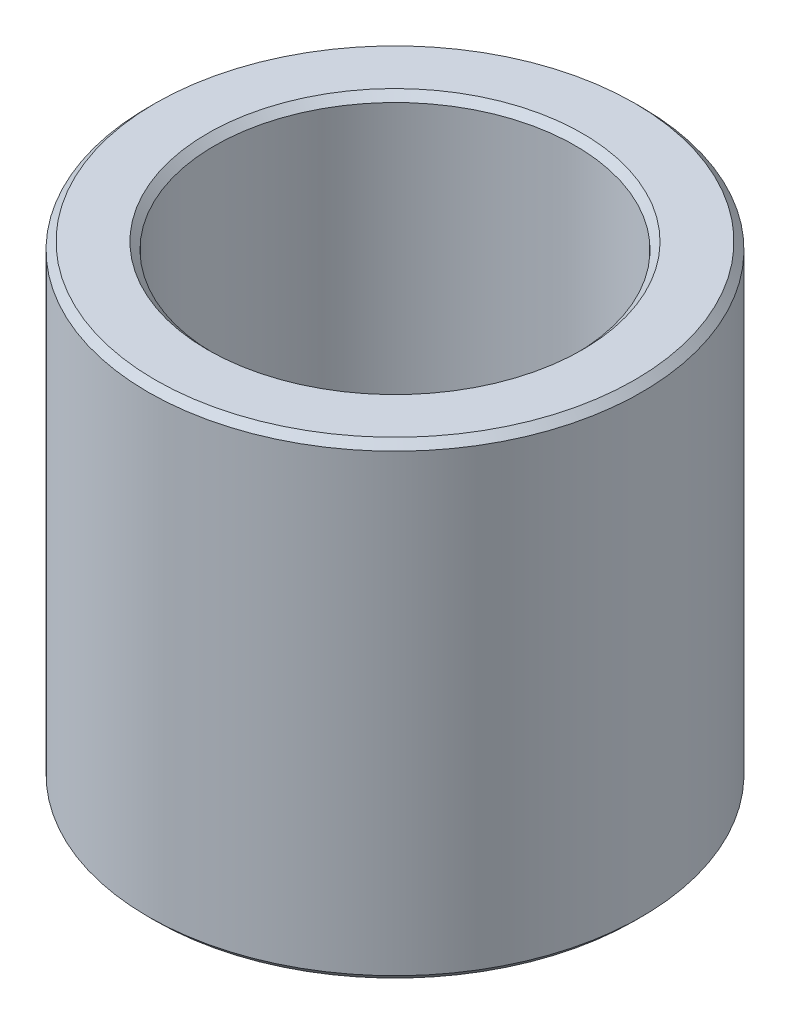
SolidWorks part; units mm, degrees
ref_plane "Front Plane" through (0, 0, 0) normal (0, 0, 1) x (1, 0, 0)
ref_plane "Top Plane" through (0, 0, 0) normal (0, 1, 0) x (1, 0, 0)
ref_plane "Right Plane" through (0, 0, 0) normal (1, 0, 0) x (0, 0, -1)
sketch "Sketch1" plane through (0, 0, 0) normal (0, 1, 0) x (1, 0, 0)
  circle A0 centre (0, 0) radius 25
  dimension "SLEEVE_OD" = 50
extrude "Boss-Extrude1" add sketch "Sketch1" along normal blind 47.45
sketch "Sketch2" plane through (0, 0, 0) normal (0, 1, 0) x (1, 0, 0)
  circle A0 centre (0, 0) radius 18.271
  dimension "BORE_D" = 36.542
extrude "Cut-Extrude1" cut sketch "Sketch2" along normal through all
chamfer "Chamfer1" distance 0.7177 angle 45 4 edges at (0, 47.45, 18.271) (0, 0, 18.271) (0, 0, 25) (0, 47.45, 25)
